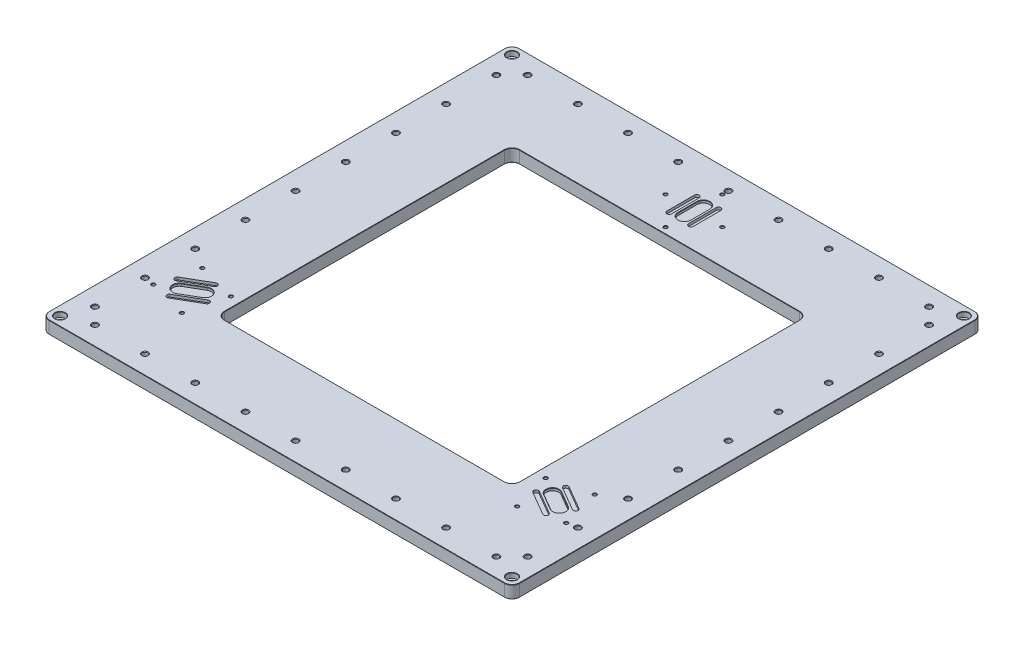
SolidWorks part; units mm, degrees
material "AISI 1045 Steel, cold drawn"
ref_plane "Front Plane" through (0, 0, 0) normal (0, 0, 1) x (1, 0, 0)
ref_plane "Top Plane" through (0, 0, 0) normal (0, 1, 0) x (1, 0, 0)
ref_plane "Right Plane" through (0, 0, 0) normal (1, 0, 0) x (0, 0, -1)
sketch "Sketch1" plane through (0, 0, 0) normal (0, 1, 0) x (1, 0, 0)
  line L1 (-187.5, -187.5) -> (187.5, -187.5)
  line L2 (-187.5, -187.5) -> (-187.5, 187.5)
  line L3 (-187.5, 187.5) -> (187.5, 187.5)
  line L4 (187.5, -187.5) -> (187.5, 187.5)
  line L5 (-187.5, -187.5) -> (187.5, 187.5) construction
  line L6 (-187.5, 187.5) -> (187.5, -187.5) construction
  point P0 (0, 0)
  dimension "D1" = 375
extrude "Boss-Extrude1" add sketch "Sketch1" along normal blind 10
hole_wizard "CBORE for M4 SHCS1" positions "Sketch4" profile "Sketch3" counterbore size "M4" standard "ANSI Metric" end condition up to next
sketch "Sketch4" plane through (0, 10, 0) normal (0, 1, 0) x (1, 0, 0)
  line L0 (0, 0) -> (-180.1218, -180.1218) construction
  line L2 (0, 0) -> (-180.1218, 0) construction
  line L3 (-180.1218, 0) -> (-180.1218, -180.1218) construction
  circle A0 centre (0, 0) radius 254.7307
  point P7 (-180.1218, -180.1218)
  dimension "D1" = 45
  dimension "D2" = 180.1218
sketch "Sketch3" plane through (-180.1218, 10, 180.1218) normal (1, 0, 0) x (0, 0, 1)
  line L0 (0, 0) -> (0, 10)
  line L1 (0, 10) -> (2.15, 10)
  line L3 (2.15, 10) -> (2.15, 4)
  line L4 (2.15, 4) -> (4, 4)
  line L5 (4, 4) -> (4, 0)
  line L7 (4, 0) -> (0, 0)
  line L11 (0, -6.35) -> (0, 107.95) construction
  dimension "Thru Hole Dia." = 4.3
  dimension "Thru Hole Depth" = 10
  dimension "C'Bore Dia." = 8
  dimension "C'Bore Depth" = 4
ref_axis "Axis1" through (0, 10.5, 0) along (0, -1, 0)
hole_wizard "M5x0.8 Tapped Hole1" positions "Sketch15" profile "Sketch16" tap size "M5x0.8" standard "ANSI Metric" end condition up to next
sketch "Sketch15" plane through (0, 10, 0) normal (0, 1, 0) x (1, 0, 0)
  line L1 (172.5, -172.5) -> (-172.5, -172.5)
  line L2 (172.5, -172.5) -> (172.5, 172.5)
  line L3 (172.5, 172.5) -> (-172.5, 172.5)
  line L4 (-172.5, -172.5) -> (-172.5, 172.5)
  line L5 (172.5, -172.5) -> (-172.5, 172.5) construction
  line L6 (172.5, 172.5) -> (-172.5, -172.5) construction
  line L9 (152, -152) -> (-152, -152) construction
  line L10 (152, -152) -> (152, 152) construction
  line L11 (152, 152) -> (-152, 152) construction
  line L12 (-152, -152) -> (-152, 152) construction
  line L13 (152, -152) -> (-152, 152) construction
  line L14 (152, 152) -> (-152, -152) construction
  point P1 (0, 0)
  point P86 (0, 0)
  point P191 (-160, 172.5)
  point P197 (-120, 172.5)
  point P198 (-80, 172.5)
  point P199 (-40, 172.5)
  point P200 (0, 172.5)
  point P201 (40, 172.5)
  point P202 (80, 172.5)
  point P203 (120, 172.5)
  point P204 (160, 172.5)
  dimension "D1" = 345
  dimension "D2" = 304
  dimension "D4" = 40
  dimension "D3" = 9
cosmetic thread "Hole Thread1" parameters "D2"=5
cosmetic thread "Hole Thread2" parameters "D2"=5
cosmetic thread "Hole Thread3" parameters "D2"=5
cosmetic thread "Hole Thread4" parameters "D2"=5
cosmetic thread "Hole Thread5" parameters "D2"=5
cosmetic thread "Hole Thread6" parameters "D2"=5
cosmetic thread "Hole Thread7" parameters "D2"=5
cosmetic thread "Hole Thread8" parameters "D2"=5
cosmetic thread "Hole Thread9" parameters "D2"=5
sketch "Sketch16" plane through (0, 10, 0) normal (1, 0, 0) x (0, 0, 1)
  line L0 (0, 0) -> (0, 10)
  line L1 (0, 10) -> (2.525, 10)
  line L2 (2.1, 9.575) -> (2.1, 0.425)
  line L3 (2.1, 0.425) -> (2.525, 0)
  line L5 (2.525, 0) -> (0, 0)
  line L6 (-2.1, 0.425) -> (-2.525, 0) construction
  line L7 (2.525, 10) -> (2.1, 9.575)
  line L8 (-2.525, 10) -> (-2.1, 9.575) construction
  line L11 (0, -6.35) -> (0, 107.95) construction
  dimension "Thru Tap Drill Dia." = 4.2
  dimension "Thru Tap Drill Depth" = 10
  dimension "Near C'Sink Dia." = 5.05
  dimension "Near C'Sink Angle" = 90
  dimension "Far C'Sink Dia." = 5.05
  dimension "Far C'Sink Angle" = 90
cosmetic thread "Hole Thread52" parameters "D2"=5
pattern_circular "CirPattern1" count 4 over 360 about axis through (0, 10.5, 0) along (0, -1, 0) of "CBORE for M4 SHCS1", "M5x0.8 Tapped Hole1"
cosmetic thread "Hole Thread12" parameters "D2"=5
cosmetic thread "Hole Thread13" parameters "D2"=5
cosmetic thread "Hole Thread14" parameters "D2"=5
cosmetic thread "Hole Thread15" parameters "D2"=5
cosmetic thread "Hole Thread16" parameters "D2"=5
cosmetic thread "Hole Thread17" parameters "D2"=5
cosmetic thread "Hole Thread18" parameters "D2"=5
cosmetic thread "Hole Thread19" parameters "D2"=5
cosmetic thread "Hole Thread20" parameters "D2"=5
cosmetic thread "Hole Thread21" parameters "D2"=5
cosmetic thread "Hole Thread22" parameters "D2"=5
cosmetic thread "Hole Thread23" parameters "D2"=5
cosmetic thread "Hole Thread24" parameters "D2"=5
cosmetic thread "Hole Thread25" parameters "D2"=5
cosmetic thread "Hole Thread26" parameters "D2"=5
cosmetic thread "Hole Thread27" parameters "D2"=5
cosmetic thread "Hole Thread28" parameters "D2"=5
cosmetic thread "Hole Thread29" parameters "D2"=5
cosmetic thread "Hole Thread30" parameters "D2"=5
cosmetic thread "Hole Thread31" parameters "D2"=5
cosmetic thread "Hole Thread32" parameters "D2"=5
cosmetic thread "Hole Thread33" parameters "D2"=5
cosmetic thread "Hole Thread34" parameters "D2"=5
cosmetic thread "Hole Thread35" parameters "D2"=5
cosmetic thread "Hole Thread36" parameters "D2"=5
cosmetic thread "Hole Thread37" parameters "D2"=5
cosmetic thread "Hole Thread38" parameters "D2"=5
sketch "Bed Holes" plane through (0, 10, 0) normal (0, 1, 0) x (1, 0, 0)
  line L0 (145, -110) -> (-145, -110) construction
  line L1 (0, -110) -> (0, 145) construction
  line L2 (152, 152) -> (152, -152) construction
  line L3 (152, 152) -> (-152, 152) construction
  line L4 (-152, 152) -> (-152, -152) construction
  line L5 (-152, -152) -> (152, -152) construction
  point P4 (0, -110)
  point P13 (0, -152)
  point P14 (152, 0)
  dimension "D1" = 255
  dimension "D2" = 7
  dimension "D3" = 304
  dimension "D4" = 7
sketch "Sketch7" plane through (0, 10, 0) normal (0, 1, 0) x (1, 0, 0)
  line L0 (-145, -110) -> (0, 145) construction
  line L1 (0, 145) -> (145, -110) construction
  line L2 (145, -110) -> (-145, -110) construction
  line L3 (-140.6453, -117.4857) -> (-149.3547, -102.5143) construction
  line L4 (-158.8629, -108.0455) -> (-139.8466, -96.983) construction
  line L5 (-159.8259, -106.3901) -> (-140.8096, -95.3276)
  line L8 (-157.8999, -109.7009) -> (-138.8836, -98.6384)
  line L11 (-95.2825, -110) -> (-120.4245, -66.781) construction
  line L12 (-150.1534, -123.017) -> (-131.1371, -111.9545) construction
  line L13 (-151.1164, -121.3616) -> (-132.1001, -110.2991)
  line L14 (0, -110) -> (0, 145) construction
  line L16 (-145, -110) -> (0, -25.6482) construction
  line L17 (0, -25.6482) -> (0, 145) construction
  line L19 (145, -110) -> (0, -25.6482) construction
  line L20 (-149.1904, -124.6724) -> (-130.1741, -113.6099)
  line L21 (0, -25.6482) -> (0, -110) construction
  line L23 (158.8629, -108.0455) -> (139.8466, -96.983) construction
  line L24 (159.8259, -106.3901) -> (140.8096, -95.3276)
  line L25 (157.8999, -109.7009) -> (138.8836, -98.6384)
  line L26 (150.1534, -123.017) -> (131.1371, -111.9545) construction
  line L27 (151.1164, -121.3616) -> (132.1001, -110.2991)
  line L28 (149.1904, -124.6724) -> (130.1741, -113.6099)
  line L29 (8.6603, 145) -> (-8.6603, 145) construction
  line L30 (-8.6603, 156) -> (-8.6603, 134) construction
  line L31 (-6.7451, 156) -> (-6.7451, 134)
  line L32 (-10.5754, 156) -> (-10.5754, 134)
  line L33 (8.6603, 156) -> (8.6603, 134) construction
  line L34 (10.5754, 156) -> (10.5754, 134)
  line L35 (6.7451, 156) -> (6.7451, 134)
  line L36 (145, -110) -> (-145, -110) construction
  arc A0 (-159.8259, -106.3901) -> (-157.8999, -109.7009) centre (-158.8629, -108.0455) ccw
  arc A1 (-138.8836, -98.6384) -> (-140.8096, -95.3276) centre (-139.8466, -96.983) ccw
  arc A2 (-151.1164, -121.3616) -> (-149.1904, -124.6724) centre (-150.1534, -123.017) ccw
  arc A3 (-130.1741, -113.6099) -> (-132.1001, -110.2991) centre (-131.1371, -111.9545) ccw
  arc A4 (159.8259, -106.3901) -> (157.8999, -109.7009) centre (158.8629, -108.0455) cw
  arc A5 (138.8836, -98.6384) -> (140.8096, -95.3276) centre (139.8466, -96.983) cw
  arc A6 (151.1164, -121.3616) -> (149.1904, -124.6724) centre (150.1534, -123.017) cw
  arc A7 (130.1741, -113.6099) -> (132.1001, -110.2991) centre (131.1371, -111.9545) cw
  arc A8 (-6.7451, 156) -> (-10.5754, 156) centre (-8.6603, 156) ccw
  arc A9 (-10.5754, 134) -> (-6.7451, 134) centre (-8.6603, 134) ccw
  arc A10 (10.5754, 156) -> (6.7451, 156) centre (8.6603, 156) ccw
  arc A11 (6.7451, 134) -> (10.5754, 134) centre (8.6603, 134) ccw
  point P5 (-149.3547, -102.5143)
  point P8 (-145, -110)
  point P17 (-140.6453, -117.4857)
  point P25 (149.3547, -102.5143)
  point P33 (140.6453, -117.4857)
  point P41 (0, 145)
  point P43 (-8.6603, 145)
  point P49 (8.6603, 145)
  point P55 (-83.0465, -110)
  point P58 (-107.8535, -88.3905)
  dimension "D4" = 22
  dimension "D3" = 1.9151
  dimension "D1" = 50
  dimension "D2" = 17.3205
extrude "Cut-Extrude2" cut sketch "Sketch7" against normal blind 2
sketch "Sketch5" plane through (0, 10, 0) normal (0, 1, 0) x (1, 0, 0)
  line L1 (117.5, -117.5) -> (-117.5, -117.5)
  line L2 (117.5, -117.5) -> (117.5, 117.5)
  line L3 (117.5, 117.5) -> (-117.5, 117.5)
  line L4 (-117.5, -117.5) -> (-117.5, 117.5)
  line L5 (117.5, -117.5) -> (-117.5, 117.5) construction
  line L6 (117.5, 117.5) -> (-117.5, -117.5) construction
  point P0 (0, 0)
  dimension "D1" = 235
extrude "Cut-Extrude3" cut sketch "Sketch5" against normal up to surface (10 mm away) up to face at (-172.5, 0, 162.525)
sketch "Sketch11" plane through (0, 10, 0) normal (0, 1, 0) x (1, 0, 0)
  line L0 (22.6274, 145) -> (0, 122.3726)
  line L1 (-133.622, -129.5587) -> (-164.5587, -121.378)
  line L2 (-133.622, -129.5587) -> (-125.4413, -98.622)
  line L3 (-125.4413, -98.622) -> (-156.378, -90.4413)
  line L4 (-164.5587, -121.378) -> (-156.378, -90.4413)
  line L5 (-133.622, -129.5587) -> (-156.378, -90.4413) construction
  line L6 (-125.4413, -98.622) -> (-164.5587, -121.378) construction
  line L7 (164.5587, -121.378) -> (133.622, -129.5587)
  line L8 (164.5587, -121.378) -> (156.378, -90.4413)
  line L9 (156.378, -90.4413) -> (125.4413, -98.622)
  line L10 (133.622, -129.5587) -> (125.4413, -98.622)
  line L11 (164.5587, -121.378) -> (125.4413, -98.622) construction
  line L12 (156.378, -90.4413) -> (133.622, -129.5587) construction
  line L13 (22.6274, 145) -> (0, 167.6274)
  line L14 (0, 122.3726) -> (-22.6274, 145)
  line L15 (0, 167.6274) -> (-22.6274, 145)
  line L16 (22.6274, 145) -> (-22.6274, 145) construction
  line L17 (0, 122.3726) -> (0, 167.6274) construction
  line L18 (0, -110) -> (0, 145) construction
  line L19 (-132.1001, -110.2991) -> (-151.1164, -121.3616) construction
  line L20 (151.1164, -121.3616) -> (132.1001, -110.2991) construction
  point P0 (-145, -110)
  point P6 (145, -110)
  point P13 (0, 145)
  dimension "D1" = 32
hole_wizard "M3x0.5 Tapped Hole1" positions "Sketch12" profile "Sketch13" tap size "M3x0.5" standard "ANSI Metric" end condition up to next
sketch "Sketch12" plane through (0, 10, 0) normal (0, 1, 0) x (1, 0, 0)
  point P0 (-164.5587, -121.378)
  point P3 (-125.4413, -98.622)
  point P6 (125.4413, -98.622)
  point P9 (164.5587, -121.378)
  point P12 (0, 122.3726)
  point P15 (0, 167.6274)
  point P19 (-156.378, -90.4413)
  point P22 (-133.622, -129.5587)
  point P25 (133.622, -129.5587)
  point P28 (156.378, -90.4413)
  point P31 (22.6274, 145)
  point P34 (-22.6274, 145)
sketch "Sketch13" plane through (-164.5587, 10, 121.378) normal (1, 0, 0) x (0, 0, 1)
  line L0 (0, 0) -> (0, 10)
  line L1 (0, 10) -> (1.25, 10)
  line L2 (1.25, 10) -> (1.25, 0.275)
  line L3 (1.25, 0.275) -> (1.525, 0)
  line L5 (1.525, 0) -> (0, 0)
  line L6 (-1.25, 0.275) -> (-1.525, 0) construction
  line L11 (0, -6.35) -> (0, 107.95) construction
  dimension "Thru Tap Drill Dia." = 2.5
  dimension "Thru Tap Drill Depth" = 10
  dimension "Near C'Sink Dia." = 3.05
  dimension "Near C'Sink Angle" = 90
cosmetic thread "Hole Thread39" parameters "D2"=3
cosmetic thread "Hole Thread40" parameters "D2"=3
cosmetic thread "Hole Thread41" parameters "D2"=3
cosmetic thread "Hole Thread42" parameters "D2"=3
cosmetic thread "Hole Thread43" parameters "D2"=3
cosmetic thread "Hole Thread44" parameters "D2"=3
cosmetic thread "Hole Thread45" parameters "D2"=3
cosmetic thread "Hole Thread46" parameters "D2"=3
cosmetic thread "Hole Thread47" parameters "D2"=3
cosmetic thread "Hole Thread48" parameters "D2"=3
cosmetic thread "Hole Thread49" parameters "D2"=3
cosmetic thread "Hole Thread50" parameters "D2"=3
sketch "Sketch14" plane through (0, 10, 0) normal (0, 1, 0) x (1, 0, 0)
  line L0 (-151.4828, -113.7713) -> (-138.5172, -106.2287) construction
  line L1 (-153.997, -109.4494) -> (-141.0314, -101.9068)
  line L2 (-148.9686, -118.0932) -> (-136.003, -110.5506)
  line L3 (151.4828, -113.7713) -> (138.5172, -106.2287) construction
  line L4 (148.9686, -118.0932) -> (136.003, -110.5506)
  line L5 (153.997, -109.4494) -> (141.0314, -101.9068)
  line L6 (0, 137.5) -> (0, 152.5) construction
  line L7 (-5, 137.5) -> (-5, 152.5)
  line L8 (5, 137.5) -> (5, 152.5)
  line L9 (-157.8999, -109.7009) -> (-138.8836, -98.6384) construction
  line L10 (138.8836, -98.6384) -> (157.8999, -109.7009) construction
  arc A3 (-153.997, -109.4494) -> (-148.9686, -118.0932) centre (-151.4828, -113.7713) ccw
  arc A4 (-136.003, -110.5506) -> (-141.0314, -101.9068) centre (-138.5172, -106.2287) ccw
  arc A5 (148.9686, -118.0932) -> (153.997, -109.4494) centre (151.4828, -113.7713) ccw
  arc A6 (141.0314, -101.9068) -> (136.003, -110.5506) centre (138.5172, -106.2287) ccw
  arc A7 (-5, 137.5) -> (5, 137.5) centre (0, 137.5) ccw
  arc A8 (5, 152.5) -> (-5, 152.5) centre (0, 152.5) ccw
  point P3 (-145, -110)
  point P12 (145, -110)
  point P20 (0, 145)
  dimension "D1" = 5
  dimension "D2" = 15
extrude "Cut-Extrude4" cut sketch "Sketch14" against normal blind 2
fillet "Fillet2" radius 6 8 edges at (-117.5, 5, 117.5) (117.5, 5, -117.5) (117.5, 5, 117.5) (-117.5, 5, -117.5) (187.5, 5, 187.5) (-187.5, 5, 187.5) (187.5, 5, -187.5) (-187.5, 5, -187.5)
chamfer "Chamfer1" distance 0.25 angle 45 48 edges at (0, 10, -132.5) (5, 10, -145) (-5, 10, -145) (0, 10, -157.5) (155.8047, 10, 116.2855) (147.5142, 10, 105.6781) (142.4858, 10, 114.3219) (134.1953, 10, 103.7145) (-134.1953, 10, 103.7145) (-147.5142, 10, 105.6781) (-142.4858, 10, 114.3219) (-155.8047, 10, 116.2855) (117.5, 0, 0) (115.7426, 0, -115.7426) (115.7426, 0, 115.7426) (0, 0, -117.5) (0, 0, 117.5) (-115.7426, 0, -115.7426) (-115.7426, 0, 115.7426) (-117.5, 0, 0) (117.5, 10, 0) (115.7426, 10, -115.7426) (115.7426, 10, 115.7426) (0, 10, -117.5) (0, 10, 117.5) (-115.7426, 10, -115.7426) (-115.7426, 10, 115.7426) (-117.5, 10, 0) (0, 0, -187.5) (-185.7426, 0, -185.7426) (185.7426, 0, -185.7426) (-187.5, 0, 0) (187.5, 0, 0) (-185.7426, 0, 185.7426) (185.7426, 0, 185.7426) (0, 0, 187.5) (0, 10, -187.5) (-185.7426, 10, -185.7426) (185.7426, 10, -185.7426) (-187.5, 10, 0) (187.5, 10, 0) (-185.7426, 10, 185.7426) (185.7426, 10, 185.7426) (0, 10, 187.5) (-180.1218, 10, -176.1218) (180.1218, 10, -176.1218) (180.1218, 10, 184.1218) (-180.1218, 10, 184.1218)
